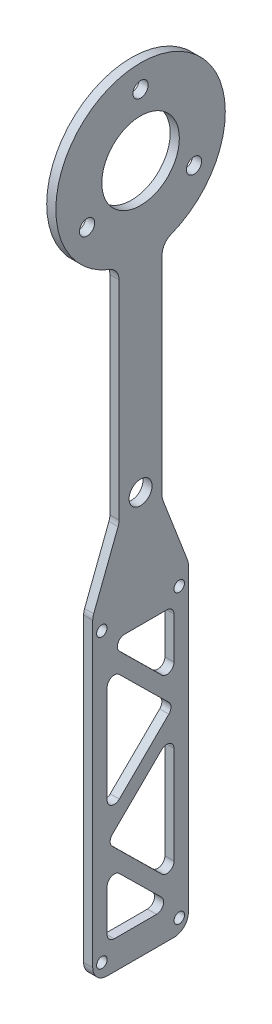
SolidWorks part; units mm, degrees
ref_plane "Front Plane" through (0, 0, 0) normal (0, 0, 1) x (1, 0, 0)
ref_plane "Top Plane" through (0, 0, 0) normal (0, 1, 0) x (1, 0, 0)
ref_plane "Right Plane" through (0, 0, 0) normal (1, 0, 0) x (0, 0, -1)
sketch "Sketch1" plane through (0, 0, 0) normal (1, 0, 0) x (0, 0, -1)
  line L0 (-13.4747, 0) -> (13.4747, 0) construction
  line L1 (0, 0) -> (0, 35) construction
  line L2 (-13.4747, 0) -> (0, 35) construction
  line L3 (0, 35) -> (13.4747, 0) construction
  line L4 (13.4747, 0) -> (-13.4747, 0) construction
  line L5 (20.7574, -5) -> (-20.7574, -5)
  line L6 (-20.7574, -5) -> (0, 48.9165)
  line L7 (0, 48.9165) -> (20.7574, -5)
  line L8 (0, 35) -> (0, 135) construction
  line L9 (0, 35) -> (0, 135) construction
  line L12 (-7.5, 35) -> (-7.5, 135)
  line L13 (7.5, 35) -> (7.5, 135)
  line L14 (-7.5, 35) -> (-7.5, 29.4356)
  line L15 (7.5, 35) -> (7.5, 29.4356)
  line L16 (-13.4747, 0) -> (13.4747, 0) construction
  line L17 (-13.4747, 0) -> (-13.4747, -100) construction
  line L18 (13.4747, 0) -> (13.4747, -100) construction
  line L19 (-13.4747, -100) -> (13.4747, -100) construction
  line L20 (-20.7574, -5) -> (20.7574, -5)
  line L21 (-20.7574, -5) -> (-20.7574, -105)
  line L22 (20.7574, -5) -> (20.7574, -105)
  line L23 (-20.7574, -105) -> (20.7574, -105)
  circle A0 centre (-13.4747, 0) radius 1.8288
  circle A1 centre (0, 35) radius 4
  circle A2 centre (13.4747, 0) radius 1.8288
  circle A3 centre (0, 135) radius 3 construction
  arc A6 (-7.5, 35) -> (7.5, 35) centre (0, 35) ccw
  arc A7 (7.5, 135) -> (-7.5, 135) centre (0, 135) ccw
  circle A8 centre (-13.4747, -100) radius 1.8288
  circle A9 centre (13.4747, -100) radius 1.8288
  circle A10 centre (0, 135) radius 21.5 construction
  circle A11 centre (0, 156.5) radius 2.65
  circle A12 centre (-18.6195, 124.25) radius 2.65
  circle A13 centre (18.6195, 124.25) radius 2.65
  arc A14 (0, 156.5) -> (-18.6195, 124.25) centre (0, 135) ccw construction
  arc A15 (0, 156.5) -> (18.6195, 124.25) centre (0, 135) cw construction
  arc A16 (-18.6195, 124.25) -> (18.6195, 124.25) centre (0, 135) ccw construction
  circle A17 centre (0, 135) radius 13.5
  circle A18 centre (0, 135) radius 29.5
  point P4 (0, 0)
  point P14 (0, 85)
  point P34 (0, 135)
  dimension "D3" = 3.6576
  dimension "D4" = 8
  dimension "D7" = 6
  dimension "D11" = 43
  dimension "D12" = 5.3
  dimension "D13" = 27
  dimension "D14" = 59
  dimension "D1" = 26.9494
  dimension "D5" = 100
  dimension "D6" = 15
  dimension "D8" = 100
  dimension "D9" = 5
  dimension "D10" = 35
  dimension "D2" = 5
extrude "Boss-Extrude1" add sketch "Sketch1" along normal blind 3.175 contours L13 A18 L12 A17 A11 A12 A13 | L12 A18 L13 A17 | A18 L12 A6 L6 L7 L13 | L6 A6 L7 A1 | A6 L6 L5 L7 A2 A0 | A6 L14 L6 | A6 L7 L15 | L21 L23 L22 L5 A9 A8 region at (0, -54.7711, 0) region at (0, 9.5725, 0) region at (0, 31.6598, -7.2402) region at (0, 31.6598, 7.2402) region at (0, 27.7524, 0) region at (0, 72.4089, 0) region at (0, 114.037, 0) region at (0, 115.1222, -8.3276)
sketch "Sketch2" plane through (3.175, 0, 0) normal (1, 0, 0) x (0, 0, -1)
  line L0 (-11.645, -5) -> (11.645, -5) construction
  line L1 (-11.645, -95) -> (11.645, -95) construction
  line L2 (11.645, -95) -> (11.645, -5) construction
  line L3 (-11.645, -95) -> (-11.645, -5) construction
  line L6 (11.645, -38.5118) -> (-11.645, -61.4882) construction
  line L7 (11.645, -5) -> (-11.645, -5)
  line L8 (-11.645, -5) -> (11.645, -27.9764)
  line L9 (11.645, -27.9764) -> (11.645, -5)
  line L10 (-11.645, -12.0236) -> (11.645, -35)
  line L11 (11.645, -35) -> (-11.645, -57.9764)
  line L12 (-11.645, -57.9764) -> (-11.645, -35)
  line L13 (-11.645, -35) -> (-11.645, -12.0236)
  line L14 (-11.645, -72.0236) -> (-11.645, -95)
  line L15 (-11.645, -95) -> (11.645, -95)
  line L16 (11.645, -95) -> (-11.645, -72.0236)
  line L17 (11.645, -42.0236) -> (11.645, -65)
  line L18 (11.645, -65) -> (11.645, -87.9764)
  line L19 (11.645, -87.9764) -> (-11.645, -65)
  line L20 (-11.645, -65) -> (11.645, -42.0236)
  line L21 (16.645, -1056.0877) -> (16.645, 48943.9123) construction
  line L22 (-16.645, -1060.2922) -> (-16.645, 48939.7078) construction
  line L23 (16.645, 29.4356) -> (-16.645, 29.4356) construction
  line L24 (-20.7574, -105) -> (-16.645, -105)
  line L25 (-20.7574, -105) -> (-20.7574, 29.4356)
  line L26 (-16.645, -105) -> (-16.645, 29.4356)
  line L27 (-20.7574, 29.4356) -> (-16.645, 29.4356)
  line L28 (-20.7574, -105) -> (20.7574, -105) construction
  line L29 (20.7574, -105) -> (16.645, -105)
  line L30 (20.7574, -105) -> (20.7574, 29.4356)
  line L31 (16.645, -105) -> (16.645, 29.4356)
  line L32 (20.7574, 29.4356) -> (16.645, 29.4356)
  circle A0 centre (13.4747, 0) radius 1.8288 construction
  circle A1 centre (13.4747, -100) radius 1.8288 construction
  point P6 (11.645, -50)
  point P10 (0, 29.4356)
  point P21 (0, -50)
  dimension "D1" = 33.29
  dimension "D2" = 5
  dimension "D3" = 5
  dimension "D4" = 5
  dimension "D5" = 5
  dimension "D6" = 2.5
  dimension "D8" = 5
  dimension "D7" = 2
extrude "Cut-Extrude1" cut sketch "Sketch2" against normal up to next
fillet "Fillet3" radius 2.5 12 edges at (1.5875, -57.9764, 11.645) (1.5875, -35, -11.645) (1.5875, -95, -11.645) (1.5875, -72.0236, 11.645) (1.5875, -95, 11.645) (1.5875, -27.9764, -11.645) (1.5875, -5, -11.645) (1.5875, -12.0236, 11.645) (1.5875, -5, 11.645) (1.5875, -87.9764, -11.645) (1.5875, -42.0236, -11.645) (1.5875, -65, 11.645)
fillet "Fillet4" radius 5 8 edges at (1.5875, 29.4356, -7.5) (1.5875, 29.4356, 7.5) (1.5875, -105, -16.645) (1.5875, -105, 16.645) (1.5875, 5.6818, 16.645) (1.5875, 5.6818, -16.645) (1.5875, 106.4693, -7.5) (1.5875, 106.4693, 7.5)
